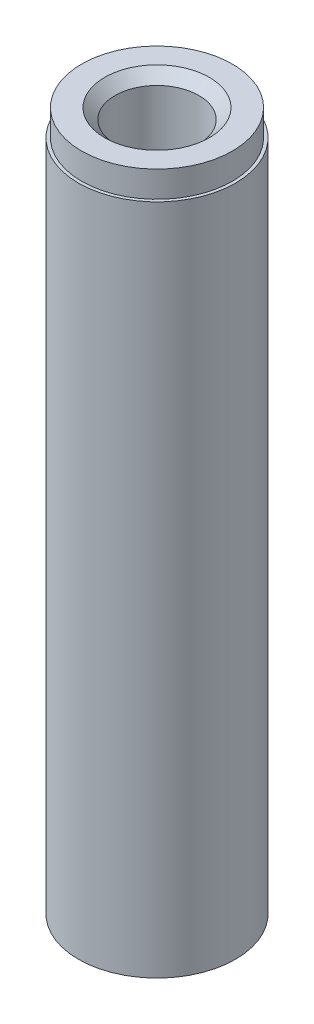
SolidWorks part; units mm, degrees
material "Natural Rubber"
ref_plane "Front Plane" through (0, 0, 0) normal (0, 0, 1) x (1, 0, 0)
ref_plane "Top Plane" through (0, 0, 0) normal (0, 1, 0) x (1, 0, 0)
ref_plane "Right Plane" through (0, 0, 0) normal (1, 0, 0) x (0, 0, -1)
sketch "Sketch1" plane through (0, 0, 0) normal (0, 1, 0) x (1, 0, 0)
  circle A0 centre (0, 0) radius 37.5
  circle A1 centre (0, 0) radius 20
  dimension "D1" = 75
  dimension "D2" = 40
extrude "Boss-Extrude1" add sketch "Sketch1" along normal blind 333.5
sketch "Sketch2" plane through (0, 333.5, 0) normal (0, 1, 0) x (1, 0, 0)
  circle A0 centre (0, 0) radius 36
  circle A1 centre (0, 0) radius 57.2901
  dimension "D1" = 72
extrude "Cut-Extrude1" cut sketch "Sketch2" against normal blind 12.5
chamfer "Chamfer2" distance 5 angle 45 1 edges at (0, 333.5, 20)
